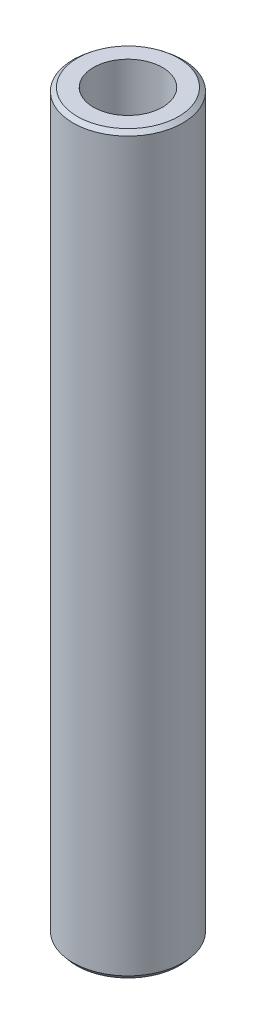
SolidWorks part; units mm, degrees
ref_plane "Front Plane" through (0, 0, 0) normal (0, 0, 1) x (1, 0, 0)
ref_plane "Top Plane" through (0, 0, 0) normal (0, 1, 0) x (1, 0, 0)
ref_plane "Right Plane" through (0, 0, 0) normal (1, 0, 0) x (0, 0, -1)
sketch "Sketch1" plane through (0, 0, 0) normal (0, 1, 0) x (1, 0, 0)
  circle A0 centre (0, 0) radius 35
  dimension "SHAFT_OD" = 70
extrude "Boss-Extrude1" add sketch "Sketch1" along normal blind 468.7226
sketch "Sketch2" plane through (0, 0, 0) normal (0, 1, 0) x (1, 0, 0)
  circle A0 centre (0, 0) radius 22.0039
  dimension "BORE_D" = 44.0078
extrude "Cut-Extrude1" cut sketch "Sketch2" along normal through all
chamfer "Chamfer1" distance 2.218 angle 50.868 2 edges at (0, 468.7226, 35) (0, 0, 35) first distance on face at (0, 468.7226, 35) first distance on face at (0, 0, 22.0039)
